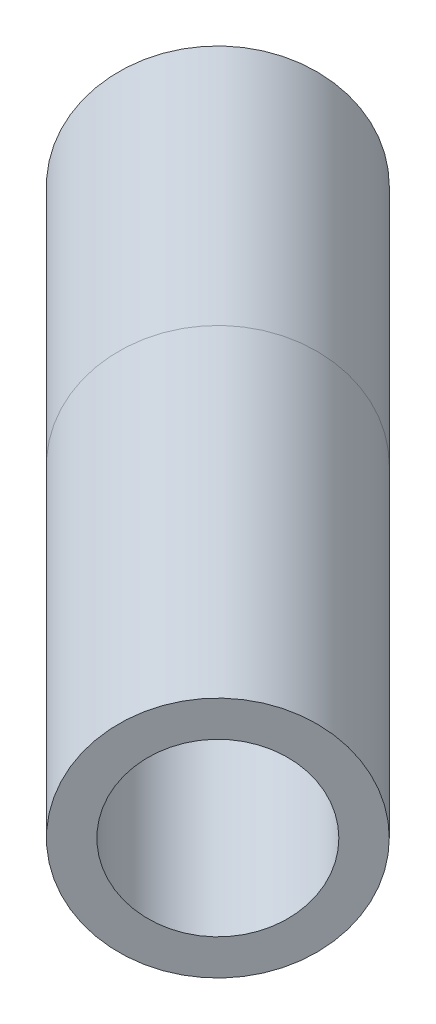
SolidWorks part; units mm, degrees
material "Silicon Rubber"
ref_plane "X-Y Datum" through (0, 0, 0) normal (0, 0, 1) x (1, 0, 0)
ref_plane "X-Z Datum" through (0, 0, 0) normal (0, 1, 0) x (1, 0, 0)
ref_plane "Y-Z Datum" through (0, 0, 0) normal (1, 0, 0) x (0, 0, -1)
sketch "Sketch1" plane through (0, 0, 0) normal (0, 1, 0) x (1, 0, 0)
  line L0 (0, 0) -> (-35.921, 35.921)
  line L1 (-35.921, 35.921) -> (-62.8618, 62.8618)
  dimension "D1" = 50.8
  dimension "D2" = 38.1
sweep "Sweep1" add path "Sketch1" circular profile diameter 26.9875 parameters "D3"=26.9875
sweep "Cut-Sweep1" cut path "Sketch1<3>" circular profile diameter 19.05 parameters "D3"=19.05
sketch "Sketch1<3>" plane through (0, 0, 0) normal (0, 1, 0) x (1, 0, 0) same geometry as "Sketch1"
